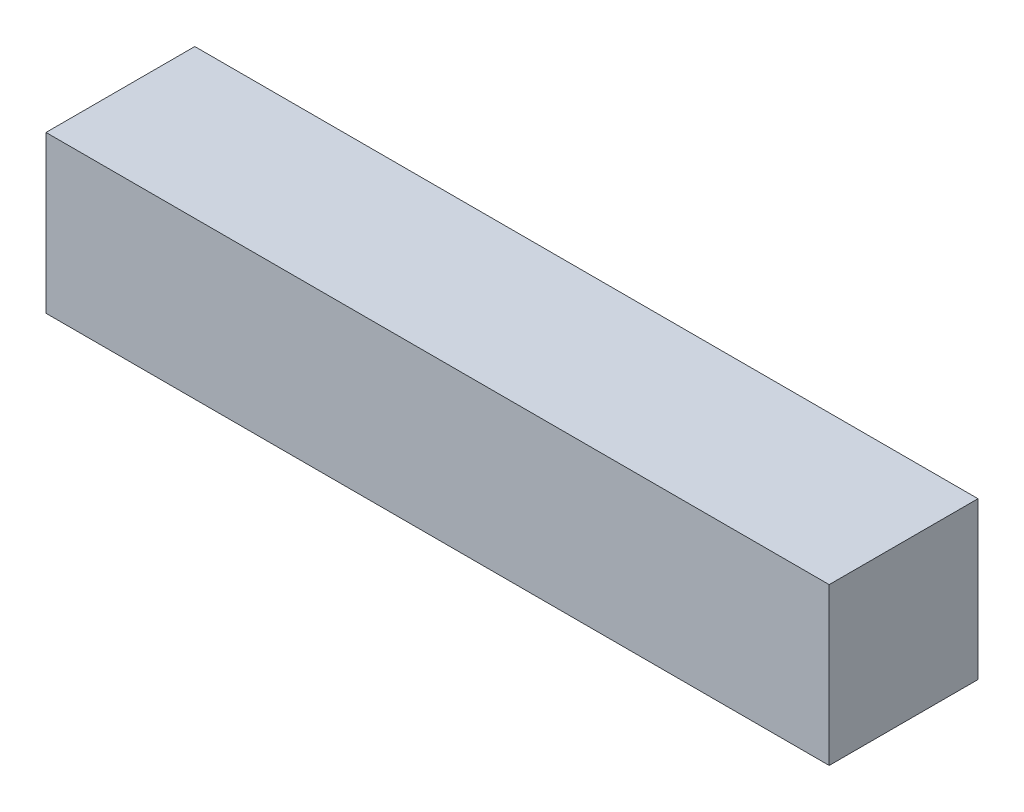
SolidWorks part; units mm, degrees
ref_plane "前基準面" through (0, 0, 0) normal (0, 0, 1) x (1, 0, 0)
ref_plane "上基準面" through (0, 0, 0) normal (0, 1, 0) x (1, 0, 0)
ref_plane "右基準面" through (0, 0, 0) normal (1, 0, 0) x (0, 0, -1)
sketch "草圖1" plane through (0, 0, 0) normal (0, 0, 1) x (1, 0, 0)
  line L1 (-50, 10) -> (50, 10)
  line L2 (-50, 10) -> (-50, -10)
  line L3 (-50, -10) -> (50, -10)
  line L4 (50, 10) -> (50, -10)
  line L5 (0, -10) -> (0, 10) construction
  line L6 (-50, 0) -> (50, 0) construction
  point P0 (0, 0)
extrude "填料-伸長1" add sketch "草圖1" along normal blind 19
extrude "填料-伸長2" add sketch "草圖1<2>" along normal blind 19
sketch "草圖1<2>" plane through (0, 0, 0) normal (0, 0, 1) x (1, 0, 0) same geometry as "草圖1"
shell "薄殼1" thickness 2 removed face at (-50, 0, 9.5)
sketch "草圖2" plane through (-50, 0, 0) normal (-1, 0, 0) x (0, 0, 1)
  line L1 (2, 8) -> (17, 8)
  line L2 (2, 8) -> (2, -8)
  line L3 (2, -8) -> (17, -8)
  line L4 (17, 8) -> (17, -8)
extrude "填料-伸長3" add sketch "草圖2" against normal blind 2
